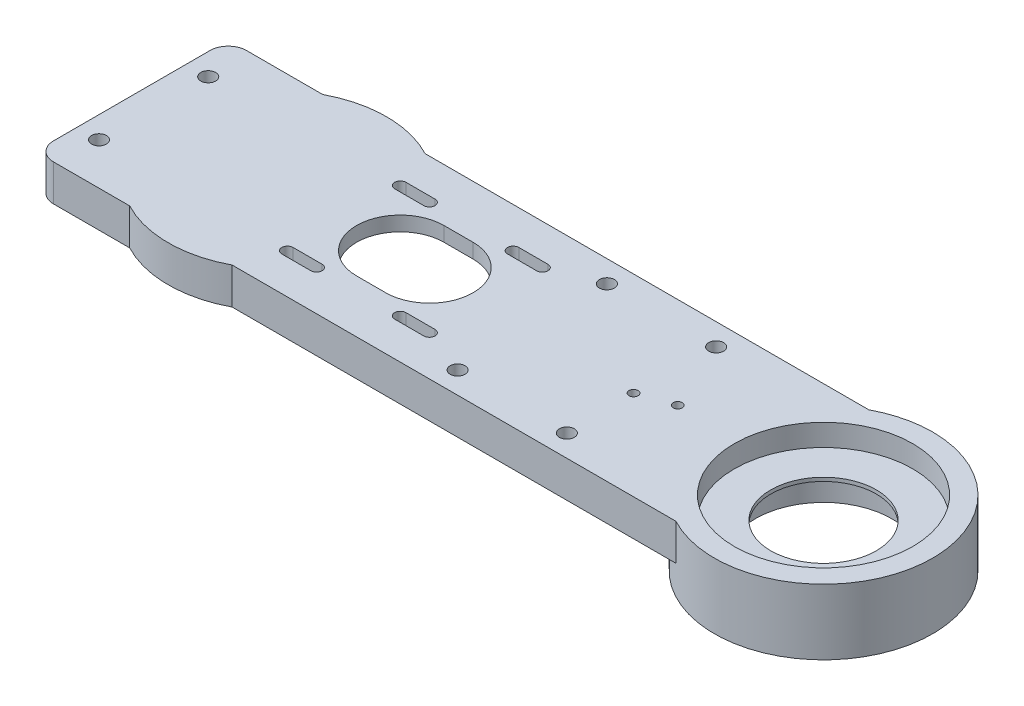
SolidWorks part; units mm, degrees
ref_plane "Front Plane" through (0, 0, 0) normal (0, 0, 1) x (1, 0, 0)
ref_plane "Top Plane" through (0, 0, 0) normal (0, 1, 0) x (1, 0, 0)
ref_plane "Right Plane" through (0, 0, 0) normal (1, 0, 0) x (0, 0, -1)
sketch "Sketch1" plane through (0, 0, 0) normal (0, 1, 0) x (1, 0, 0)
  line L0 (-75, 0) -> (75, 0) construction
  line L1 (-52.1363, 26.5) -> (60.9376, 26.5)
  line L3 (-52.1363, -26.5) -> (60.9376, -26.5)
  line L4 (-52.1363, 26.5) -> (-60.9376, 26.5)
  line L5 (-52.1363, -26.5) -> (-60.9376, -26.5)
  arc A1 (60.9376, -26.5) -> (60.9376, 26.5) centre (75, 0) ccw
  arc A2 (-60.9376, 26.5) -> (-60.9376, -26.5) centre (-75, 0) ccw
  point P0 (0, 0)
  point P1 (0, 0)
  dimension "D3" = 60
  dimension "D4" = 60
  dimension "D1" = 150
  dimension "D2" = 53
extrude "Boss-Extrude1" add sketch "Sketch1" along normal blind 10
sketch "Sketch2" plane through (0, 0, 0) normal (0, -1, 0) x (1, 0, 0)
  line L5 (-62.25, 21.2726) -> (-12.25, 21.2726)
  line L6 (-62.25, 21.2726) -> (-62.25, -21.2274)
  line L7 (-62.25, -21.2274) -> (-12.25, -21.2274)
  line L8 (-12.25, 21.2726) -> (-12.25, -21.2274)
  line L9 (-62.25, 21.2726) -> (-12.25, -21.2274) construction
  line L10 (-62.25, -21.2274) -> (-12.25, 21.2726) construction
  dimension "D1" = 50
  dimension "D2" = 42.5
  dimension "D4" = 12.25
extrude "Cut-Extrude1" cut sketch "Sketch2" against normal blind 6 contours L5 L8 L7 L6
sketch "Sketch10" plane through (0, 0, 0) normal (0, -1, 0) x (1, 0, 0)
  circle A0 centre (75, 0) radius 14.5
  dimension "D1" = 29
extrude "Cut-Extrude7" cut sketch "Sketch10" against normal up to next
sketch "Sketch11" plane through (0, 0, 0) normal (0, -1, 0) x (1, 0, 0)
  circle A0 centre (75, 0) radius 18.75
  dimension "D1" = 37.5
extrude "Cut-Extrude8" cut sketch "Sketch11" against normal blind 3 and the other way through all
sketch "Sketch12" plane through (0, 0, 0) normal (0, -1, 0) x (1, 0, 0)
  circle A1 centre (75, 0) radius 30
extrude "Boss-Extrude3" add sketch "Sketch12" along normal blind 8
sketch "Sketch13" plane through (0, -8, 0) normal (0, -1, 0) x (1, 0, 0)
  circle A0 centre (75, 0) radius 24.5
  dimension "D1" = 49
extrude "Cut-Extrude9" cut sketch "Sketch13" against normal blind 3
sketch "Sketch14" plane through (0, -5, 0) normal (0, -1, 0) x (1, 0, 0)
  circle A0 centre (75, 0) radius 18.75
  dimension "D1" = 37.5
extrude "Cut-Extrude10" cut sketch "Sketch14" against normal blind 7
sketch "Sketch15" plane through (0, 10, 0) normal (0, 1, 0) x (1, 0, 0)
  circle A0 centre (75, 0) radius 24.5
  dimension "D1" = 49
extrude "Cut-Extrude11" cut sketch "Sketch15" against normal blind 6
sketch "Sketch25" plane through (0, 6, 0) normal (0, -1, 0) x (1, 0, 0)
  line L0 (-33.25, 0) -> (-41.25, 0) construction
  line L1 (-33.25, -12) -> (-41.25, -12)
  line L2 (-33.25, 12) -> (-41.25, 12)
  line L3 (-12.25, 21.2726) -> (-12.25, -21.2274) construction
  line L4 (-17.75, -15.5) -> (-25.75, -15.5) construction
  line L5 (-17.75, -15.5) -> (-48.75, -15.5) construction
  line L6 (-17.75, -15.5) -> (-17.75, 15.5) construction
  line L7 (-17.75, 15.5) -> (-48.75, 15.5) construction
  line L8 (-48.75, -15.5) -> (-48.75, 15.5) construction
  line L9 (-17.75, -15.5) -> (-48.75, 15.5) construction
  line L10 (-17.75, 15.5) -> (-48.75, -15.5) construction
  line L11 (-25.75, -15.5) -> (-56.75, -15.5) construction
  line L12 (-25.75, -15.5) -> (-25.75, 15.5) construction
  line L13 (-25.75, 15.5) -> (-56.75, 15.5) construction
  line L14 (-56.75, -15.5) -> (-56.75, 15.5) construction
  line L15 (-25.75, -15.5) -> (-56.75, 15.5) construction
  line L16 (-25.75, 15.5) -> (-56.75, -15.5) construction
  line L17 (-17.75, -17.05) -> (-25.75, -17.05)
  line L18 (-17.75, -13.95) -> (-25.75, -13.95)
  line L19 (-48.75, -15.5) -> (-56.75, -15.5) construction
  line L20 (-48.75, -17.05) -> (-56.75, -17.05)
  line L21 (-48.75, -13.95) -> (-56.75, -13.95)
  line L22 (-48.75, 15.5) -> (-56.75, 15.5) construction
  line L23 (-48.75, 13.95) -> (-56.75, 13.95)
  line L24 (-48.75, 17.05) -> (-56.75, 17.05)
  line L25 (-17.75, 15.5) -> (-25.75, 15.5) construction
  line L26 (-17.75, 13.95) -> (-25.75, 13.95)
  line L27 (-17.75, 17.05) -> (-25.75, 17.05)
  arc A0 (-33.25, -12) -> (-33.25, 12) centre (-33.25, 0) ccw
  arc A1 (-41.25, 12) -> (-41.25, -12) centre (-41.25, 0) ccw
  arc A2 (-17.75, -17.05) -> (-17.75, -13.95) centre (-17.75, -15.5) ccw
  arc A3 (-25.75, -13.95) -> (-25.75, -17.05) centre (-25.75, -15.5) ccw
  arc A4 (-48.75, -17.05) -> (-48.75, -13.95) centre (-48.75, -15.5) ccw
  arc A5 (-56.75, -13.95) -> (-56.75, -17.05) centre (-56.75, -15.5) ccw
  arc A6 (-48.75, 13.95) -> (-48.75, 17.05) centre (-48.75, 15.5) ccw
  arc A7 (-56.75, 17.05) -> (-56.75, 13.95) centre (-56.75, 15.5) ccw
  arc A8 (-17.75, 13.95) -> (-17.75, 17.05) centre (-17.75, 15.5) ccw
  arc A9 (-25.75, 17.05) -> (-25.75, 13.95) centre (-25.75, 15.5) ccw
  point P3 (-37.25, 0)
  point P10 (-33.25, 0)
  point P15 (-41.25, 0)
  point P20 (-21.75, -15.5)
  point P25 (-52.75, -15.5)
  point P30 (-52.75, 15.5)
  point P35 (-21.75, 15.5)
  dimension "D2" = 21
  dimension "D1" = 8
  dimension "D3" = 31
  dimension "D4" = 31
  dimension "D5" = 31
  dimension "D6" = 31
  dimension "D7" = 3.1
  dimension "D8" = 3.1
  dimension "D9" = 3.1
  dimension "D10" = 3.1
extrude "Cut-Extrude19" cut sketch "Sketch25" against normal up to next
sketch "Sketch26" plane through (0, 10, 0) normal (0, 1, 0) x (1, 0, 0)
  line L1 (-75, -26.5) -> (-115, -26.5)
  line L2 (-75, -26.5) -> (-75, 26.5)
  line L3 (-75, 26.5) -> (-115, 26.5)
  line L4 (-115, -26.5) -> (-115, 26.5)
  circle A0 centre (-75, 0) radius 14.8337 construction
  point P7 (-75, 0)
  dimension "D1" = 53
  dimension "D2" = 40
extrude "Boss-Extrude5" add sketch "Sketch26" against normal blind 10
ref_axis "Axis1" through (-75, 10, 0) along (0, -1, 0)
sketch "Sketch19" plane through (0, 10, 0) normal (0, 1, 0) x (1, 0, 0)
  line L1 (-68.5166, 26.5) -> (-115, 26.5)
  line L2 (-68.5166, 26.5) -> (-68.5166, -26.5)
  line L3 (-68.5166, -26.5) -> (-115, -26.5)
  line L4 (-115, 26.5) -> (-115, -26.5)
  line L5 (-68.5166, 26.5) -> (-115, -26.5) construction
  line L6 (-68.5166, -26.5) -> (-115, 26.5) construction
  point P0 (-91.7583, 0)
  dimension "D1" = 53
  dimension "D2" = 40
extrude "Boss-Extrude4" add sketch "Sketch19" against normal blind 10
sketch "Sketch23" plane through (0, 0, 0) normal (0, -1, 0) x (1, 0, 0)
  line L1 (-62.25, -21.2274) -> (-69.25, -21.2274)
  line L2 (-62.25, -21.2274) -> (-62.25, 21.25)
  line L3 (-62.25, 21.25) -> (-69.25, 21.25)
  line L4 (-69.25, -21.2274) -> (-69.25, 21.25)
  dimension "D1" = 7
extrude "Cut-Extrude18" cut sketch "Sketch23" against normal blind 6
fillet "Fillet3" radius 5 2 edges at (-115, 5, 26.5) (-115, 5, -26.5)
sketch "Sketch27" plane through (0, 10, 0) normal (0, 1, 0) x (1, 0, 0)
  line L0 (25, -20.5) -> (-5, -20.5) construction
  line L1 (-60.9376, -26.5) -> (60.9376, -26.5) construction
  circle A0 centre (25, -20.5) radius 2.05
  circle A1 centre (-5, -20.5) radius 2.05
  circle A2 centre (75, 0) radius 4.9626
  dimension "D1" = 4.1
  dimension "D2" = 4.1
  dimension "D3" = 6
  dimension "D4" = 30
  dimension "D5" = 50
extrude "Cut-Extrude20" cut sketch "Sketch27" against normal blind 20
sketch "Sketch29" plane through (0, 0, 0) normal (0, -1, 0) x (1, 0, 0)
  line L0 (-109, -15) -> (-109, 15) construction
  line L1 (-115, -21.5) -> (-115, 21.5) construction
  circle A0 centre (-109, -15) radius 2.05
  circle A1 centre (-109, 15) radius 2.05
  point P3 (-109, 0)
  dimension "D2" = 4.1
  dimension "D3" = 4.1
  dimension "D1" = 30
  dimension "D4" = 6
extrude "Cut-Extrude22" cut sketch "Sketch29" against normal up to next
mirror "Mirror2" about plane through (0, 0, 0) normal (0, 0, 1) of "Cut-Extrude20"
sketch "Sketch30" plane through (0, 0, 0) normal (0, -1, 0) x (1, 0, 0)
  line L0 (24.664, 1.8452) -> (33.6149, -1.338) construction
  circle A0 centre (24.664, 1.8452) radius 1.25
  circle A1 centre (33.6149, -1.338) radius 1.25
  dimension "D1" = 2.5
  dimension "D2" = 2.5
  dimension "D3" = 9.5
extrude "Cut-Extrude23" cut sketch "Sketch30" against normal up to next
